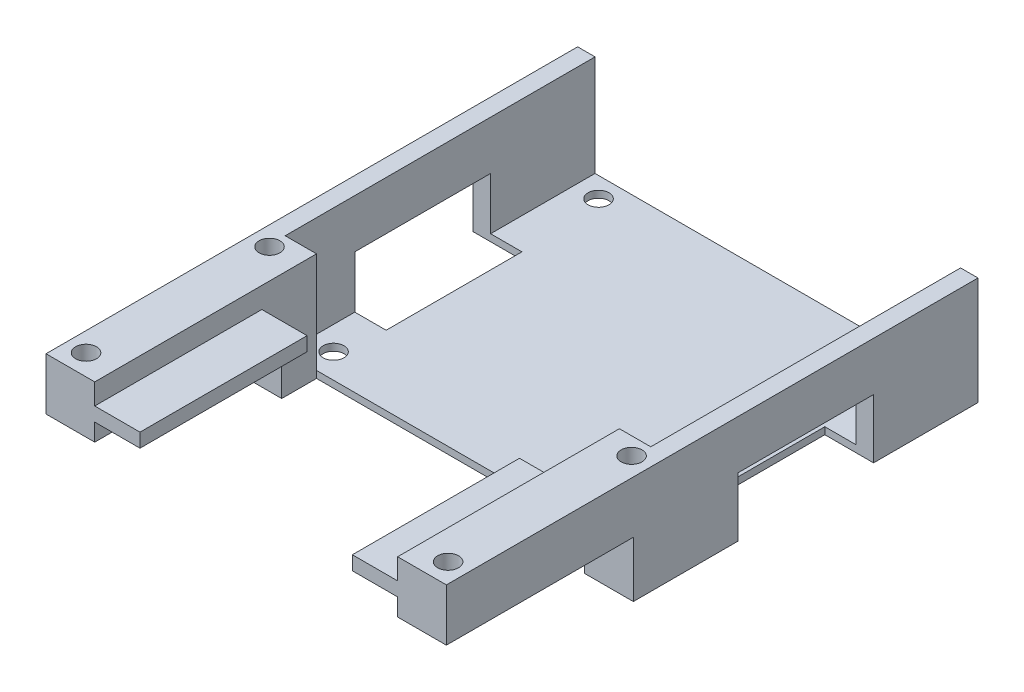
SolidWorks part; units mm, degrees
ref_plane "Front Plane" through (0, 0, 0) normal (0, 0, 1) x (1, 0, 0)
ref_plane "Top Plane" through (0, 0, 0) normal (0, 1, 0) x (1, 0, 0)
ref_plane "Right Plane" through (0, 0, 0) normal (1, 0, 0) x (0, 0, -1)
sketch "Sketch1" plane through (0, 0, 0) normal (0, 1, 0) x (1, 0, 0)
  line L0 (0, 0) -> (0, 76.35) construction
  line L1 (-28.75, 76.35) -> (28.75, 76.35)
  line L2 (28.75, 76.35) -> (28.75, 0)
  line L3 (28.75, 0) -> (21.75, 0)
  line L4 (21.75, 0) -> (21.75, 31.85)
  line L5 (21.75, 31.85) -> (-21.75, 31.85)
  line L6 (-21.75, 31.85) -> (-21.75, 0)
  line L7 (-21.75, 0) -> (-28.75, 0)
  line L8 (-28.75, 0) -> (-28.75, 76.35)
  line L9 (-26.25, 76.35) -> (-26.25, 31.85)
  line L14 (-26.25, 31.85) -> (-21.75, 31.85)
  line L15 (26.25, 76.35) -> (26.25, 31.85)
  line L16 (26.25, 31.85) -> (21.75, 31.85)
  line L17 (28.75, 74.35) -> (30.25, 74.35)
  line L18 (-28.75, 41.35) -> (-26.25, 41.35)
  line L19 (-28.75, 41.35) -> (-28.75, 53.35)
  line L20 (-28.75, 53.35) -> (-26.25, 53.35)
  line L21 (-26.25, 41.35) -> (-26.25, 53.35)
  line L22 (30.25, 68.35) -> (28.75, 68.35)
  line L23 (-30.25, 68.35) -> (-28.75, 68.35)
  line L24 (-28.75, 74.35) -> (-30.25, 74.35)
  arc A0 (30.25, 68.35) -> (30.25, 74.35) centre (30.25, 71.35) ccw
  arc A1 (-30.25, 68.35) -> (-30.25, 74.35) centre (-30.25, 71.35) cw
  point P10 (0, 76.35)
  point P16 (-27.5, 41.35)
  point P17 (-22.85, 73.45)
  point P18 (22.85, 73.45)
  point P23 (22.85, 35.4)
  point P24 (-22.85, 35.4)
  point P25 (26, 3)
  point P26 (26, 29.35)
  point P27 (-26, 29.35)
  point P28 (-26, 3)
  point P40 (30.25, 71.35)
  point P41 (-30.25, 71.35)
  dimension "D16" = 3
  dimension "D1" = 2.5
  dimension "D2" = 7
  dimension "D3" = 43.5
  dimension "D4" = 31.85
  dimension "D5" = 44.5
  dimension "D6" = 23
  dimension "D7" = 12
  dimension "D8" = 22.85
  dimension "D9" = 38.05
  dimension "D10" = 2.9
  dimension "D11" = 52
  dimension "D12" = 52
  dimension "D13" = 47
  dimension "D14" = 3
  dimension "D15" = 1.5
  dimension "D17" = 2
extrude "Boss-Extrude1" add sketch "Sketch1" along normal blind 1 contours L5 L0 L1 L9 L14 | L0 L5 L16 L15 L1 region at (-13.125, 0, -54.1) region at (13.125, 0, -54.1)
extrude "Boss-Extrude2" add sketch "Sketch1<3>" along normal blind 15.5 contours L18 L8 L7 L6 L14 L9 | L8 L20 L9 L1 | L15 L16 L4 L3 L2 L1 | L20 L8 L18 L9 region at (-27.5, 0, -64.85) region at (25.999, 0, -28.6329) region at (-27.5, 0, -47.35) region at (-25.4666, 0, -17.9154)
sketch "Sketch1<3>" plane through (0, 0, 0) normal (0, 1, 0) x (1, 0, 0) same geometry as "Sketch1"
hole_wizard "Ø3.0 (3) Diameter Hole1" positions "Sketch4" profile "Sketch5" hole size "Ø3.0" standard "ANSI Metric" end condition through all
sketch "Sketch4" plane through (0, 0, 0) normal (0, -1, 0) x (-1, 0, 0)
  point P0 (-22.85, 73.45)
  point P3 (22.85, 73.45)
  point P6 (26, 29.35)
  point P9 (22.85, 35.4)
  point P12 (-22.85, 35.4)
  point P15 (-26, 29.35)
  point P18 (-26, 3)
  point P21 (26, 3)
  point P24 (-30.25, 71.35)
  point P27 (30.25, 71.35)
sketch "Sketch5" plane through (22.85, 0, -73.45) normal (1, 0, 0) x (0, 0, -1)
  line L0 (0, 0) -> (0, 15.5)
  line L1 (0, 15.5) -> (1.5, 15.5)
  line L2 (1.5, 15.5) -> (1.5, 0)
  line L5 (1.5, 0) -> (0, 0)
  line L11 (0, -6.35) -> (0, 107.95) construction
  dimension "Thru Hole Dia." = 3
  dimension "Thru Hole Depth" = 15.5
sketch "Sketch6" plane through (0, 0, 0) normal (0, 0, 1) x (1, 0, 0)
  line L0 (-21.75, 15.5) -> (-21.75, 0) construction
  line L5 (0, -1.6497) -> (0, 21.9352) construction
  line L6 (-21.75, 10.5) -> (-15.25, 10.5)
  line L7 (-21.75, 10.5) -> (-21.75, 12.5)
  line L8 (-21.75, 12.5) -> (-15.25, 12.5)
  line L9 (-15.25, 10.5) -> (-15.25, 12.5)
  line L10 (-28.75, 15.5) -> (-28.75, 0) construction
  line L11 (-20.25, 10.5) -> (-21.75, 10.5)
  line L12 (-20.25, 10.5) -> (-20.25, 8)
  line L13 (-20.25, 8) -> (-21.75, 8)
  line L14 (-21.75, 10.5) -> (-21.75, 8)
  line L15 (-21.75, 0) -> (-28.75, 0)
  line L16 (-21.75, 0) -> (-21.75, 8)
  line L17 (-21.75, 8) -> (-28.75, 8)
  line L18 (-28.75, 0) -> (-28.75, 8)
  line L19 (28.75, 0) -> (28.75, 8)
  line L20 (21.75, 8) -> (28.75, 8)
  line L21 (21.75, 0) -> (21.75, 8)
  line L22 (21.75, 0) -> (28.75, 0)
  line L23 (21.75, 10.5) -> (21.75, 8)
  line L24 (20.25, 8) -> (21.75, 8)
  line L25 (20.25, 10.5) -> (20.25, 8)
  line L26 (20.25, 10.5) -> (21.75, 10.5)
  line L27 (15.25, 10.5) -> (15.25, 12.5)
  line L28 (21.75, 12.5) -> (15.25, 12.5)
  line L29 (21.75, 10.5) -> (21.75, 12.5)
  line L30 (21.75, 10.5) -> (15.25, 10.5)
  line L31 (-21.75, 15.5) -> (-28.75, 15.5) construction
  line M21 (21.75, 0) -> (28.75, 0)
  line M22 (28.75, 0) -> (28.75, 15.5)
  line M24 (21.75, 15.5) -> (21.75, 0)
  dimension "D1" = 6.5
  dimension "D2" = 3
  dimension "D3" = 2
  dimension "D4" = 2.5
  dimension "D5" = 1.5
extrude "Boss-Extrude3" add sketch "Sketch6" against normal blind 24 contours L30 L26 L28 L27 M24 | L6 L9 L8 L7 region at (-18.5, 11.5, 0) region at (18.5, 11.5, 0)
extrude "Cut-Extrude1" cut sketch "Sketch6<4>" against normal blind 26.85 contours L18 L15 L16 L17 | L20 M24 M21 M22 region at (-25.25, 4, 0) region at (25.25, 4, 0)
sketch "Sketch6<4>" plane through (0, 0, 0) normal (0, 0, 1) x (1, 0, 0) same geometry as "Sketch6"
sketch "Sketch8" plane through (0, 0, 0) normal (0, -1, 0) x (1, 0, 0)
  line L0 (0, 17.5937) -> (0, -89.2896) construction
  line L1 (-28.75, -61.35) -> (-21.75, -61.35)
  line L2 (-28.75, -61.35) -> (-28.75, -41.85)
  line L3 (-28.75, -41.85) -> (-21.75, -41.85)
  line L4 (-21.75, -61.35) -> (-21.75, -41.85)
  line L6 (-28.75, -76.35) -> (28.75, -76.35) construction
  line L8 (21.75, -61.35) -> (21.75, -41.85)
  line L9 (28.75, -41.85) -> (21.75, -41.85)
  line L10 (28.75, -61.35) -> (28.75, -41.85)
  line L11 (28.75, -61.35) -> (21.75, -61.35)
  line L12 (-28.75, -26.85) -> (-28.75, -76.35) construction
  dimension "D1" = 15
  dimension "D2" = 7
  dimension "D3" = 19.5
extrude "Cut-Extrude2" cut sketch "Sketch8" against normal blind 8.5
sketch "Sketch9" plane through (0, 0, 0) normal (0, -1, 0) x (1, 0, 0)
  line L0 (-3.426, -67.9209) -> (-1.4298, -56.6)
  line L1 (-1.4298, -56.6) -> (-9.4298, -56.6)
  line L2 (-9.4298, -56.6) -> (3.426, -41.2791)
  line L3 (3.426, -41.2791) -> (1.4298, -52.6)
  line L4 (1.4298, -52.6) -> (9.4298, -52.6)
  line L5 (9.4298, -52.6) -> (-3.426, -67.9209)
  line L6 (-1.4298, -56.6) -> (1.4298, -52.6) construction
  line L7 (-21.75, -61.35) -> (-21.75, -41.85) construction
  line L8 (-10.502, -57.1) -> (4.2424, -39.5283)
  line L9 (4.2424, -39.5283) -> (2.0257, -52.1)
  line L10 (2.0257, -52.1) -> (10.502, -52.1)
  line L11 (10.502, -52.1) -> (-4.2424, -69.6717)
  line L12 (-4.2424, -69.6717) -> (-2.0257, -57.1)
  line L13 (-2.0257, -57.1) -> (-10.502, -57.1)
  line L14 (-21.75, -51.6) -> (21.75, -51.6) construction
  line L15 (21.75, -41.85) -> (21.75, -61.35) construction
  point P2 (0, -54.6)
  dimension "D1" = 50
  dimension "D2" = 50
  dimension "D3" = 30
  dimension "D4" = 30
  dimension "D5" = 4
  dimension "D6" = 20
  dimension "D7" = 20
  dimension "D8" = 8
  dimension "D10" = 3
  dimension "D9" = 0.5
extrude "Cut-Extrude3" cut sketch "Sketch9" against normal blind 0.3
equation "\"D1@Boss-Extrude2\"=16.000000mm-0.5"
equation "\"D7@Sketch9\"=\"D6@Sketch9\""
equation "\"D2@Sketch9\"=\"D1@Sketch9\""
equation "\"D4@Sketch9\"=\"D3@Sketch9\""
